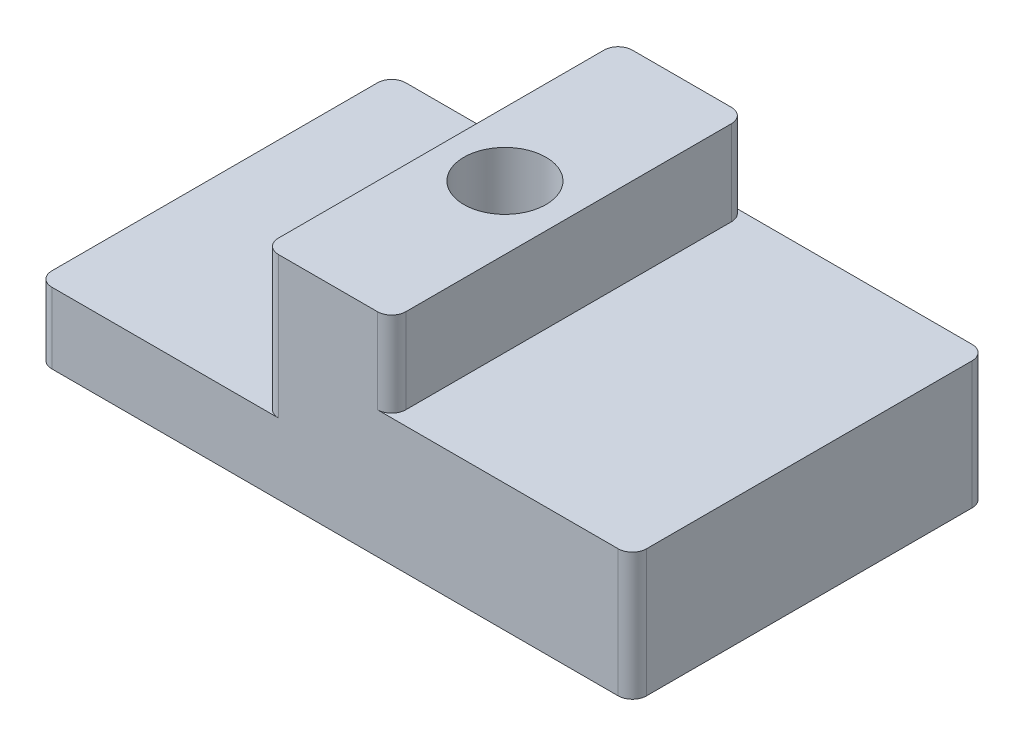
SolidWorks part; units mm, degrees
ref_plane "Front Plane" through (0, 0, 0) normal (0, 0, 1) x (1, 0, 0)
ref_plane "Top Plane" through (0, 0, 0) normal (0, 1, 0) x (1, 0, 0)
ref_plane "Right Plane" through (0, 0, 0) normal (1, 0, 0) x (0, 0, -1)
sketch "Sketch1" plane through (0, 0, 0) normal (0, 1, 0) x (1, 0, 0)
  line L1 (0, 0) -> (45, 0)
  line L2 (0, 0) -> (0, 25)
  line L3 (0, 25) -> (45, 25)
  line L4 (45, 0) -> (45, 25)
  dimension "D1" = 45
  dimension "D2" = 25
extrude "Boss-Extrude1" add sketch "Sketch1" along normal blind 5 contours L1 L4 L3 L2 region at (22.5, 0, -12.5)
sketch "Sketch5" plane through (0, 5, 0) normal (0, 1, 0) x (1, 0, 0)
  line L0 (0, 25) -> (45, 25) construction
  line L1 (19, 25) -> (45, 25)
  line L2 (19, 25) -> (19, 0)
  line L3 (19, 0) -> (45, 0)
  line L4 (45, 25) -> (45, 0)
  line L5 (45, 0) -> (45, 25) construction
  line L6 (0, 0) -> (45, 0) construction
  dimension "D1" = 26
extrude "Boss-Extrude3" add sketch "Sketch5" along normal blind 4
sketch "Sketch11" plane through (0, 9, 0) normal (0, 1, 0) x (1, 0, 0)
  line L0 (19, 25) -> (19, 0) construction
  line L1 (19, 25) -> (28, 25)
  line L2 (19, 25) -> (19, 0)
  line L3 (19, 0) -> (28, 0)
  line L4 (28, 25) -> (28, 0)
  line L5 (45, 25) -> (19, 25) construction
  line L6 (19, 0) -> (45, 0) construction
  dimension "D1" = 9
extrude "Boss-Extrude5" add sketch "Sketch11" along normal blind 6
sketch "Sketch12" plane through (0, 5, 0) normal (0, 1, 0) x (1, 0, 0)
  line L0 (0, 25) -> (19, 25) construction
  line L1 (0, 25) -> (3, 25)
  line L2 (0, 25) -> (0, 0)
  line L3 (0, 0) -> (3, 0)
  line L4 (3, 25) -> (3, 0)
  line L5 (0, 0) -> (0, 25) construction
  line L6 (0, 0) -> (19, 0) construction
  dimension "D1" = 3
extrude "Cut-Extrude2" cut sketch "Sketch12" against normal through all
sketch "Sketch13" plane through (0, 0, 0) normal (0, -1, 0) x (-1, 0, 0)
  line L0 (-23.5, 0) -> (-23.5, 25) construction
  line L1 (-3, 0) -> (-45, 0) construction
  line L2 (-3, 25) -> (-45, 25) construction
  line L3 (-45, 0) -> (-45, 25) construction
  point P8 (-23.5, 12.5)
  dimension "D1" = 21.5
hole_wizard "M5 Clearance Hole1" positions "Sketch14" profile "Sketch15" hole size "M5" standard "ISO" end condition through all
sketch "Sketch14" plane through (0, 0, 0) normal (0, -1, 0) x (-1, 0, 0)
  point P0 (-23.5, 12.5)
sketch "Sketch15" plane through (23.5, 0, -12.5) normal (1, 0, 0) x (0, 0, -1)
  line L0 (0, 0) -> (0, 15)
  line L1 (0, 15) -> (2.9, 15)
  line L2 (2.9, 15) -> (2.9, 0)
  line L5 (2.9, 0) -> (0, 0)
  line L11 (0, -6.35) -> (0, 107.95) construction
  dimension "Thru Hole Dia." = 5.8
  dimension "Thru Hole Depth" = 15
fillet "Fillet2" radius 1 8 edges at (28, 12, 0) (19, 10, 0) (19, 10, -25) (28, 12, -25) (3, 2.5, -25) (3, 2.5, 0) (45, 4.5, 0) (45, 4.5, -25)
